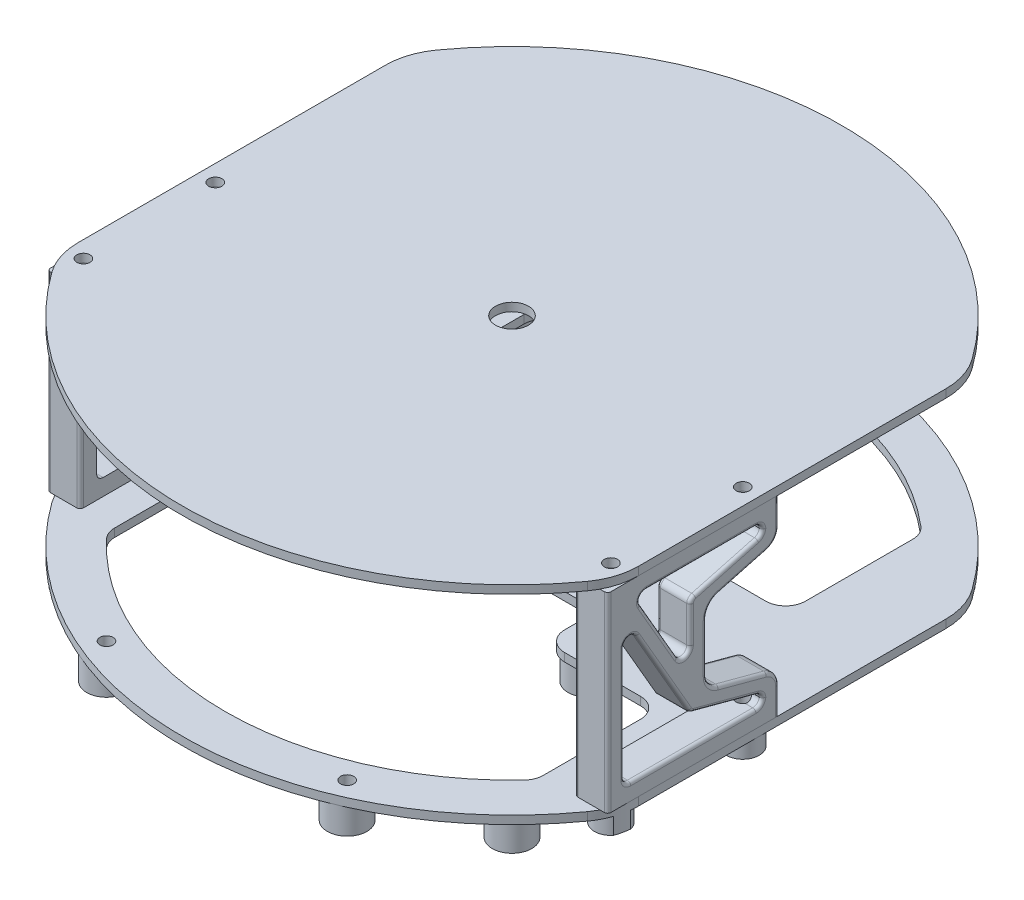
SolidWorks part; units mm, degrees
ref_plane "Front" through (0, 0, 0) normal (0, 0, 1) x (1, 0, 0)
ref_plane "Top" through (0, 0, 0) normal (0, 1, 0) x (1, 0, 0)
ref_plane "Right" through (0, 0, 0) normal (1, 0, 0) x (0, 0, -1)
sketch "Sketch1" plane through (0, 0, 0) normal (0, 1, 0) x (1, 0, 0)
  line L0 (0, 71.1393) -> (0, -87.7098) construction
  line L1 (-42.5, 26.3391) -> (-42.5, -26.3391)
  line L2 (42.5, 26.3391) -> (42.5, -26.3391)
  arc A0 (-42.5, -26.3391) -> (42.5, -26.3391) centre (0, 0) ccw
  arc A1 (42.5, 26.3391) -> (-42.5, 26.3391) centre (0, 0) ccw
  dimension "D1" = 100
  dimension "D2" = 85
extrude "Boss-Extrude1" add sketch "Sketch1" along normal blind 1.25
sketch "Sketch2" plane through (0, 0, 0) normal (0, -1, 0) x (1, 0, 0)
  line L0 (0, 45.5144) -> (0, -63.1722) construction
  line L1 (-51.2989, 0) -> (55.2567, 0) construction
  circle A0 centre (-33, 33) radius 3
  circle A2 centre (-33, 33) radius 1.125
  circle A4 centre (-33, -33) radius 1.125
  circle A5 centre (-33, -33) radius 3
  circle A6 centre (33, -33) radius 3
  circle A7 centre (33, -33) radius 1.125
  circle A8 centre (33, 33) radius 1.125
  circle A9 centre (33, 33) radius 3
  dimension "D3" = 2.25
  dimension "D4" = 6
  dimension "D1" = 66
  dimension "D2" = 66
extrude "Boss-Extrude2" add sketch "Sketch2" along normal blind 4
fillet "Fillet1" radius 10 4 edges at (-42.5, 0.625, -26.3391) (-42.5, 0.625, 26.3391) (42.5, 0.625, -26.3391) (42.5, 0.625, 26.3391)
sketch "Sketch3" plane through (0, 1.25, 0) normal (0, 1, 0) x (1, 0, 0)
  line L0 (0, 58.0627) -> (0, -62.1815) construction
  line L1 (-18.25, -6.75) -> (18.25, -6.75) construction
  line L2 (-18.25, -6.75) -> (-18.25, -43.25) construction
  line L3 (-18.25, -43.25) -> (18.25, -43.25) construction
  line L4 (18.25, -6.75) -> (18.25, -43.25) construction
  line L5 (-18.25, -6.75) -> (18.25, -43.25) construction
  line L6 (-18.25, -43.25) -> (18.25, -6.75) construction
  circle A0 centre (-18.25, -6.75) radius 1
  circle A1 centre (18.25, -6.75) radius 1
  circle A2 centre (18.25, -43.25) radius 1
  circle A3 centre (-18.25, -43.25) radius 1
  circle A4 centre (-40, -5) radius 1
  circle A5 centre (-40, -25) radius 1
  circle A6 centre (40, -25) radius 1
  circle A7 centre (40, -5) radius 1
  point P0 (0, -25)
  dimension "D1" = 2
  dimension "D2" = 36.5
  dimension "D3" = 25
  dimension "D4" = 20
  dimension "D5" = 80
  dimension "D6" = 0
sketch "Sketch4" plane through (0, 0, 0) normal (0, -1, 0) x (1, 0, 0)
  circle A0 centre (-18.25, 43.25) radius 3
  circle A1 centre (18.25, 43.25) radius 3
  circle A2 centre (18.25, 6.75) radius 3
  circle A3 centre (-18.25, 6.75) radius 3
  circle A4 centre (-40, 25) radius 2.5
  circle A5 centre (-40, 5) radius 2.5
  circle A6 centre (40, 25) radius 2.5
  circle A7 centre (40, 5) radius 2.5
  arc M10 (42.5, 23.3184) -> (40.625, 29.1481) centre (32.5, 23.3184) ccw
  arc M16 (-40.625, 29.1481) -> (-42.5, 23.3184) centre (-32.5, 23.3184) ccw
  dimension "D1" = 6
  dimension "D2" = 5
extrude "Boss-Extrude3" add sketch "Sketch4" along normal up to surface (4 mm away) contours A3 | A0 | A1 | A2 region at (-18.25, 0, 43.25) region at (18.25, 0, 43.25) region at (18.25, 0, 6.75) region at (-18.25, 0, 6.75) up to face at (-33, -4, 30)
extrude "Boss-Extrude7" add sketch "Sketch4<3>" along normal offset from surface (2.5 mm away) 1.5 contours A4 M16 | A6 M10 | A5 | A7 region at (-39.9675, 0, 24.9927) region at (39.9675, 0, 24.9927) up to face at (18.25, -4, 3.75)
sketch "Sketch4<3>" plane through (0, 0, 0) normal (0, -1, 0) x (1, 0, 0) same geometry as "Sketch4"
extrude "Cut-Extrude1" cut sketch "Sketch3" against normal through all
sketch "Sketch6" plane through (0, 0, 0) normal (0, -1, 0) x (1, 0, 0)
  line L0 (-29.5, -32.6458) -> (-29.5, -12)
  line L1 (-29.5, -12) -> (-6, -12)
  line L2 (29.5, -12) -> (29.5, -32.6458)
  line L3 (0, 0) -> (0, -57.2909) construction
  line L4 (-32.5, 28.9137) -> (-32.5, 10)
  line L5 (-32.5, 10) -> (-15, 10)
  line L6 (32.5, 10) -> (32.5, 28.9137)
  line L7 (-6, -12) -> (-6, -43.589)
  line L8 (6, -12) -> (6, -43.589)
  line L9 (6, -12) -> (29.5, -12)
  line L10 (15, 10) -> (32.5, 10)
  line L12 (-15, 10) -> (-15, 2)
  line L13 (-15, 2) -> (15, 2)
  line L14 (15, 10) -> (15, 2)
  arc A0 (-29.5, -32.6458) -> (-6, -43.589) centre (0, 0) ccw
  arc A1 (-40.625, -29.1481) -> (40.625, -29.1481) centre (0, 0) ccw construction
  arc A2 (-32.5, 28.9137) -> (32.5, 28.9137) centre (0, 0) cw
  arc A3 (40.625, 29.1481) -> (-40.625, 29.1481) centre (0, 0) ccw construction
  arc A4 (6, -43.589) -> (29.5, -32.6458) centre (0, 0) ccw
  dimension "D2" = 6
  dimension "D4" = 6.5
  dimension "D1" = 59
  dimension "D3" = 12
  dimension "D5" = 10
  dimension "D6" = 12
  dimension "D7" = 65
  dimension "D8" = 8
  dimension "D9" = 30
extrude "Cut-Extrude2" cut sketch "Sketch6" against normal through all
fillet "Fillet2" radius 3 16 edges at (-29.5, 0.625, -12) (-6, 0.625, -12) (-6, 0.625, -43.589) (29.5, 0.625, -12) (29.5, 0.625, -32.6458) (6, 0.625, -43.589) (6, 0.625, -12) (-29.5, 0.625, -32.6458) (32.5, 0.625, 28.9137) (-32.5, 0.625, 28.9137) (-32.5, 0.625, 10) (32.5, 0.625, 10) (15, 0.625, 2) (15, 0.625, 10) (-15, 0.625, 2) (-15, 0.625, 10)
ref_point "Point1"
ref_plane "Plane1" through (-40, 0, 0) normal (-1, 0, 0) x (0, 0, 1)
sketch "Sketch7" plane through (-40, 0, 0) normal (-1, 0, 0) x (0, 0, 1)
  line L0 (2, 1.25) -> (2, 7.25)
  line L1 (-23.3184, 1.25) -> (23.3184, 1.25) construction
  line L2 (2, 7.25) -> (13, 10.1974)
  line L3 (13, 10.1974) -> (13, 21.3026)
  line L4 (13, 21.3026) -> (2, 24.25)
  line L5 (2, 24.25) -> (2, 30.25)
  line L6 (2, 30.25) -> (28, 30.25)
  line L7 (28, 30.25) -> (28, 1.25)
  line L8 (28, 1.25) -> (2, 1.25)
  line L9 (4.5, 27.75) -> (23.8548, 27.75)
  line L11 (25.5, 3.75) -> (4.5, 3.75)
  line L12 (4.5, 3.75) -> (4.5, 5.3317)
  line L13 (4.5, 5.3317) -> (15.5, 8.2791)
  line L14 (15.5, 13.2791) -> (15.5, 23.2209)
  line L15 (15.5, 23.2209) -> (4.5, 26.1683)
  line L16 (4.5, 26.1683) -> (4.5, 27.75)
  line L17 (15.5, 8.2791) -> (25.5, 25.5996)
  line L19 (23.8548, 27.75) -> (15.5, 13.2791)
  line L21 (15.5, 8.2791) -> (15.5, 23.2209) construction
  line L22 (25.5, 25.5996) -> (25.5, 3.75)
  line L23 (25.5, 27.75) -> (25.5, 3.75) construction
  line L24 (4.5, 27.75) -> (25.5, 27.75) construction
  dimension "D1" = 2
  dimension "D2" = 26
  dimension "D3" = 15
  dimension "D4" = 15
  dimension "D5" = 15
  dimension "D6" = 6
  dimension "D7" = 29
  dimension "D9" = 2.5
  dimension "D10" = 30
  dimension "D8" = 2.5
extrude "Boss-Extrude4" add sketch "Sketch7" along normal mid plane 5 separate body
fillet "Fillet3" radius 2.5 4 edges at (-40, 7.25, 2) (-40, 10.1974, 13) (-40, 21.3026, 13) (-40, 24.25, 2)
fillet "Fillet4" radius 1 10 edges at (-40, 25.5996, 25.5) (-40, 8.2791, 15.5) (-40, 5.3317, 4.5) (-40, 3.75, 25.5) (-40, 3.75, 4.5) (-40, 13.2791, 15.5) (-40, 27.75, 4.5) (-40, 26.1683, 4.5) (-40, 23.2209, 15.5) (-40, 27.75, 23.8548)
fillet "Fillet5" radius 0.5 47 edges at (-37.5, 15.75, 28) (-37.5, 3.2908, 2) (-37.5, 6.8536, 2.5166) (-37.5, 8.7237, 7.5) (-37.5, 10.5939, 12.4834) (-37.5, 15.75, 13) (-37.5, 20.9061, 12.4834) (-37.5, 22.7763, 7.5) (-37.5, 24.6464, 2.5166) (-37.5, 28.2092, 2) (-42.5, 3.2908, 2) (-42.5, 6.8536, 2.5166) (-42.5, 8.7237, 7.5) (-42.5, 10.5939, 12.4834) (-42.5, 15.75, 13) (-42.5, 20.9061, 12.4834) (-42.5, 22.7763, 7.5) (-42.5, 24.6464, 2.5166) (-42.5, 28.2092, 2) (-42.5, 15.75, 28) (-42.5, 4.0108, 4.8265) (-42.5, 5.2093, 4.7358) (-42.5, 6.8511, 10.1705) (-42.5, 8.3445, 15.4498) (-42.5, 15.5027, 19.6705) (-42.5, 22.8335, 24.7588) (-42.5, 13.3088, 25.5) (-42.5, 4.0429, 25.2071) (-42.5, 3.75, 15) (-37.5, 27.4892, 4.8265) (-42.5, 27.4892, 4.8265) (-37.5, 26.2907, 4.7358) (-37.5, 24.6946, 10) (-37.5, 23.0623, 15.2934) (-37.5, 19.7324, 15.5) (-37.5, 16.0452, 16.2412) (-42.5, 26.2907, 4.7358) (-42.5, 24.6946, 10) (-42.5, 23.0623, 15.2934) (-42.5, 19.7324, 15.5) (-42.5, 16.0452, 16.2412) (-37.5, 27.75, 13.8114) (-42.5, 27.75, 13.8114) (-37.5, 21.3806, 20.1774) (-42.5, 21.3806, 20.1774) (-37.5, 27.25, 22.9887) (-42.5, 27.25, 22.9887)
sketch "Sketch8" plane through (0, 1.25, 0) normal (0, -1, 0) x (1, 0, 0)
  circle A2 centre (-40, 5) radius 1
  circle A3 centre (-40, 25) radius 1
extrude "Cut-Extrude3" cut sketch "Sketch8" against normal blind 3.5
extrude "Cut-Extrude4" cut sketch "Sketch8<3>" along normal blind 3.5 from surface starting at face at (-40, 30.25, 15)
sketch "Sketch8<3>" plane through (0, 1.25, 0) normal (0, -1, 0) x (1, 0, 0) same geometry as "Sketch8"
mirror "Mirror1" about plane through (0, 0, 0) normal (1, 0, 0) of bodies 109
sketch "Sketch9" plane through (0, 30.25, 0) normal (0, 1, 0) x (1, 0, 0)
  line L0 (-42.5, 23.3184) -> (-42.5, -23.3184) construction
  line L1 (42.5, -23.3184) -> (42.5, 23.3184) construction
  line L2 (-42.5, 23.3184) -> (-42.5, -23.3184)
  line L3 (42.5, -23.3184) -> (42.5, 23.3184)
  arc A0 (40.625, 29.1481) -> (-40.625, 29.1481) centre (0, 0) ccw construction
  arc A1 (-40.625, 29.1481) -> (-42.5, 23.3184) centre (-32.5, 23.3184) ccw construction
  arc A2 (-42.5, -23.3184) -> (-40.625, -29.1481) centre (-32.5, -23.3184) ccw construction
  arc A3 (-40.625, -29.1481) -> (40.625, -29.1481) centre (0, 0) ccw construction
  arc A4 (40.625, -29.1481) -> (42.5, -23.3184) centre (32.5, -23.3184) ccw construction
  arc A5 (42.5, 23.3184) -> (40.625, 29.1481) centre (32.5, 23.3184) ccw construction
  arc A6 (-40.625, 29.1481) -> (-42.5, 23.3184) centre (-32.5, 23.3184) ccw
  arc A7 (-42.5, -23.3184) -> (-40.625, -29.1481) centre (-32.5, -23.3184) ccw
  arc A8 (-40.625, -29.1481) -> (40.625, -29.1481) centre (0, 0) ccw
  arc A9 (40.625, -29.1481) -> (42.5, -23.3184) centre (32.5, -23.3184) ccw
  arc A10 (42.5, 23.3184) -> (40.625, 29.1481) centre (32.5, 23.3184) ccw
  arc A11 (40.625, 29.1481) -> (-40.625, 29.1481) centre (0, 0) ccw
  circle A12 centre (0, 0) radius 2.5
  dimension "D1" = 5
extrude "Boss-Extrude6" add sketch "Sketch9" along normal blind 1.25 separate body
sketch "Sketch10" plane through (0, 30.25, 0) normal (0, -1, 0) x (1, 0, 0)
  line L0 (0, 53.912) -> (0, -58.3807) construction
  circle A0 centre (-40, 5) radius 1 construction
  circle A1 centre (-40, 25) radius 1 construction
  circle A2 centre (-40, 5) radius 1
  circle A3 centre (-40, 25) radius 1
  circle A4 centre (40, 25) radius 1
  circle A5 centre (40, 5) radius 1
extrude "Cut-Extrude5" cut sketch "Sketch10" against normal through all
sketch "Sketch11" plane through (0, 31.5, 0) normal (0, 1, 0) x (1, 0, 0)
  line L0 (0, 0) -> (0, 40) construction
  line L1 (0, 40) -> (-30.3109, 22.5) construction
  line L2 (0, 40) -> (30.3109, 22.5) construction
  circle A0 centre (0, 40) radius 1.5
  circle A1 centre (-15.1554, 31.25) radius 1.5
  circle A2 centre (-30.3109, 22.5) radius 1.5
  circle A3 centre (15.1554, 31.25) radius 1.5
  circle A4 centre (30.3109, 22.5) radius 1.5
  circle A5 centre (0, -25) radius 1.5
  dimension "D4" = 3
  dimension "D1" = 120
  dimension "D2" = 40
  dimension "D3" = 35
  dimension "D5" = 25
extrude "Cut-Extrude6" [suppressed] cut sketch "Sketch11" against normal up to next
equation "\"D5@Sketch7\"=\"D4@Sketch7\""
